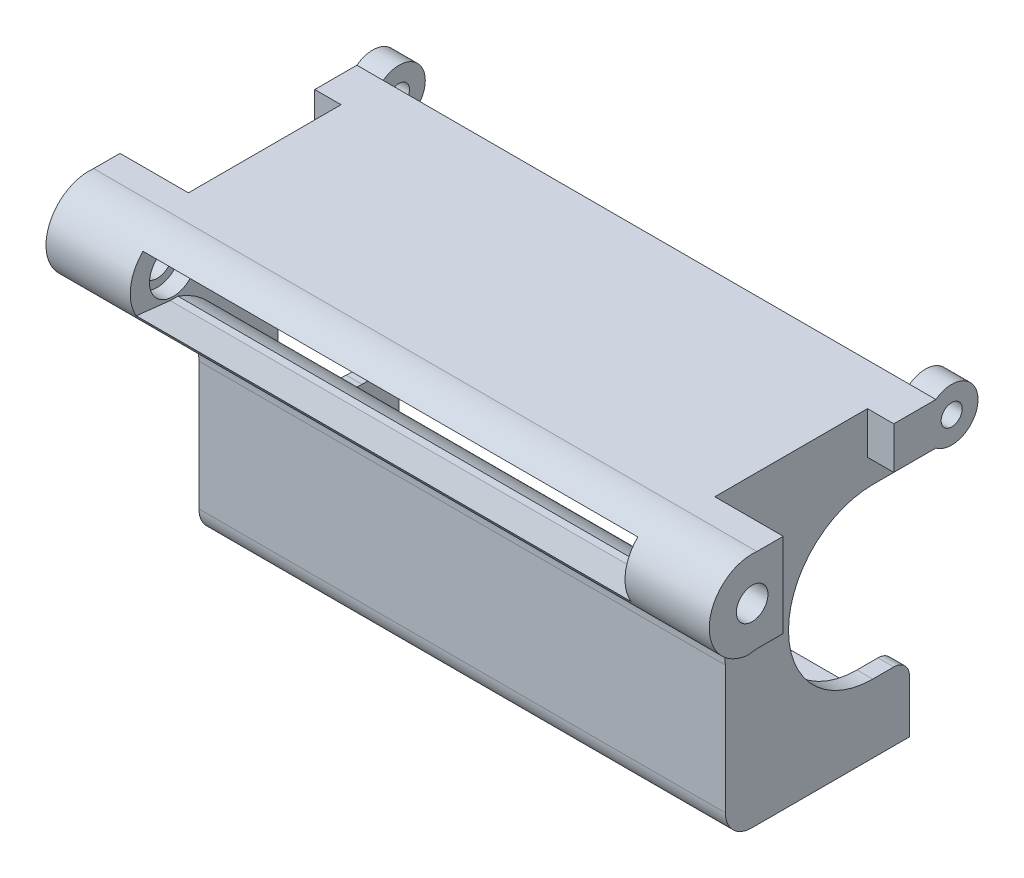
SolidWorks part; units mm, degrees
ref_plane "前视基准面" through (0, 0, 0) normal (0, 0, 1) x (1, 0, 0)
ref_plane "上视基准面" through (0, 0, 0) normal (0, 1, 0) x (1, 0, 0)
ref_plane "右视基准面" through (0, 0, 0) normal (1, 0, 0) x (0, 0, -1)
sketch "草图1" plane through (0, 0, 0) normal (0, 0, 1) x (1, 0, 0)
  line L1 (63, -8) -> (-63, -8)
  line L2 (63, -8) -> (63, 8)
  line L3 (63, 8) -> (-63, 8)
  line L4 (-63, -8) -> (-63, 8)
  line L5 (63, -8) -> (-63, 8) construction
  line L6 (63, 8) -> (-63, -8) construction
  line L7 (60, -5) -> (-60, -5)
  line L8 (60, -5) -> (60, 5)
  line L9 (60, 5) -> (-60, 5)
  line L10 (-60, -5) -> (-60, 5)
  line L11 (60, -5) -> (-60, 5) construction
  line L12 (60, 5) -> (-60, -5) construction
  point P0 (0, 0)
  point P6 (0, 0)
  dimension "D1" = 3
  dimension "D2" = 3
extrude "凸台-拉伸1" add sketch "草图1" along normal blind 70
sketch "草图2" plane through (0, 0, 70) normal (0, 0, 1) x (1, 0, 0)
  line L0 (0, 5) -> (0, -5) construction
  line L1 (60, 5) -> (-60, 5) construction
  line L2 (-60, -5) -> (60, -5) construction
  line L4 (2.7049, -5) -> (-2.7049, -5)
  line L5 (2.7049, -5) -> (2.7049, 5)
  line L6 (2.7049, 5) -> (-2.7049, 5)
  line L7 (-2.7049, -5) -> (-2.7049, 5)
  line L8 (2.7049, -5) -> (-2.7049, 5) construction
  line L9 (2.7049, 5) -> (-2.7049, -5) construction
  point P6 (0, 0)
extrude "凸台-拉伸2" add sketch "草图2" against normal blind 70
fillet "圆角4" radius 3 1 edges at (-2.7049, -5, 35)
fillet "圆角5" radius 3 1 edges at (-2.7049, 5, 35)
ref_plane "基准面1" through (0, 0, 2) normal (0, 0, -1) x (-1, 0, 0)
sketch "草图5" plane through (0, 0, 2) normal (0, 0, -1) x (-1, 0, 0)
  line L0 (-72, 0) -> (-69, 0) construction
  line L1 (-63, -8) -> (-63, 8) construction
  line L3 (-63, 3.5) -> (-63, -3.5)
  line L4 (-63, -3.5) -> (-72, -3.5)
  line L6 (-63, 3.5) -> (-72, 3.5)
  line L7 (-72, -3.5) -> (-72, 3.5)
  line L8 (-63, 0) -> (-72, 3.5) construction
  line L9 (-63, 0) -> (-72, -3.5) construction
  circle A1 centre (-69, 0) radius 1.6
  dimension "D1" = 9
extrude "凸台-拉伸3" add sketch "草图5" against normal blind 4
fillet "圆角7" radius 2 4 edges at (63, -3.5, 4) (72, -3.5, 4) (72, 3.5, 4) (63, 3.5, 4)
mirror "镜向8" about plane through (0, 0, 0) normal (1, 0, 0) of bodies 108
ref_plane "基准面3" through (0, 0, 35) normal (0, 0, -1) x (-1, 0, 0)
mirror "镜向11" about plane through (0, 0, 35) normal (0, 0, -1) of bodies 112
sketch "草图7" plane through (0, -8, 0) normal (0, -1, 0) x (1, 0, 0)
  line L0 (0, 0) -> (0, 70) construction
  line L1 (-63, 70) -> (63, 70) construction
  line L2 (-25, 0) -> (-25, 70) construction
  line L3 (-63, 0) -> (63, 0) construction
  line L4 (-42, 0) -> (-42, 70) construction
  line L5 (-63, 6) -> (63, 6) construction
  line L6 (-63, 9) -> (63, 9) construction
  line L7 (-63, 70) -> (-63, 0) construction
  line L8 (63, 70) -> (63, 0) construction
  line L9 (-43.6, 21) -> (-43.6, 9)
  line L10 (-40.4, 21) -> (-40.4, 9)
  line L11 (-42, 70) -> (-25, 70) construction
  line L12 (-33.5, 70) -> (-33.5, 0) construction
  line L13 (-26.6, 21) -> (-26.6, 9)
  line L14 (-23.4, 21) -> (-23.4, 9)
  line L15 (23.4, 21) -> (23.4, 9)
  line L16 (26.6, 21) -> (26.6, 9)
  line L17 (40.4, 21) -> (40.4, 9)
  line L18 (43.6, 21) -> (43.6, 9)
  arc A0 (-43.6, 9) -> (-40.4, 9) centre (-42, 9) ccw
  arc A1 (-40.4, 21) -> (-43.6, 21) centre (-42, 21) ccw
  arc A2 (-26.6, 21) -> (-23.4, 21) centre (-25, 21) cw
  arc A3 (-23.4, 9) -> (-26.6, 9) centre (-25, 9) cw
  arc A4 (23.4, 9) -> (26.6, 9) centre (25, 9) ccw
  arc A5 (26.6, 21) -> (23.4, 21) centre (25, 21) ccw
  arc A6 (40.4, 21) -> (43.6, 21) centre (42, 21) cw
  arc A7 (43.6, 9) -> (40.4, 9) centre (42, 9) cw
  dimension "D4" = 12
  dimension "D1" = 25
  dimension "D2" = 17
  dimension "D3" = 3
extrude "切除-拉伸2" cut sketch "草图7" against normal blind 4
fillet "圆角11" radius 2 12 edges at (-32.8524, 5, 0) (-3.5835, 4.1213, 0) (-32.8524, -5, 0) (-3.5835, -4.1213, 0) (32.8524, -5, 0) (3.5835, -4.1213, 0) (32.8524, 5, 0) (3.5835, 4.1213, 0) (60, 0, 0) (-60, 0, 0) (-2.7049, 0, 0) (2.7049, 0, 0)
fillet "圆角12" radius 2 12 edges at (-32.8524, 5, 70) (-3.5835, 4.1213, 70) (-2.7049, 0, 70) (-3.5835, -4.1213, 70) (32.8524, 5, 70) (3.5835, 4.1213, 70) (2.7049, 0, 70) (3.5835, -4.1213, 70) (-60, 0, 70) (-32.8524, -5, 70) (60, 0, 70) (32.8524, -5, 70)
ref_plane "基准面4" through (0, 0, -10) normal (0, 0, -1) x (-1, 0, 0)
sketch "草图9" plane through (0, 0, -10) normal (0, 0, -1) x (-1, 0, 0)
  line L1 (63, -8) -> (-63, -8)
  line L2 (63, -8) -> (63, 8)
  line L3 (63, 8) -> (-63, 8)
  line L4 (-63, -8) -> (-63, 8)
  line L5 (60, -5) -> (-60, -5)
  line L6 (60, -5) -> (60, 5)
  line L7 (60, 5) -> (-60, 5)
  line L8 (-60, -5) -> (-60, 5)
extrude "凸台-拉伸4" add sketch "草图9" along normal blind 5 separate body
sketch "草图10" plane through (0, 0, -10) normal (0, 0, -1) x (-1, 0, 0)
  line L0 (-63, -8) -> (63, -8) construction
  line L1 (-50, 8) -> (50, 8)
  line L2 (-50, 8) -> (-50, -8)
  line L3 (-50, -8) -> (50, -8)
  line L4 (50, 8) -> (50, -8)
  line L5 (-50, 8) -> (50, -8) construction
  line L6 (-50, -8) -> (50, 8) construction
  line L7 (-60, -5) -> (60, -5) construction
  line L8 (-47, 5) -> (47, 5)
  line L9 (-47, 5) -> (-47, -5)
  line L10 (-47, -5) -> (47, -5)
  line L11 (47, 5) -> (47, -5)
  line L12 (-47, 5) -> (47, -5) construction
  line L13 (-47, -5) -> (47, 5) construction
  point P0 (0, 0)
  point P8 (0, 0)
  dimension "D1" = 3
  dimension "D2" = 100
extrude "凸台-拉伸5" add sketch "草图10" along normal blind 7
sketch "草图11" plane through (0, 0, -15) normal (0, 0, -1) x (-1, 0, 0)
  line L0 (50, -8) -> (50, 8) construction
  line L1 (60, -5) -> (50, -5)
  line L2 (60, -5) -> (60, 5)
  line L3 (60, 5) -> (50, 5)
  line L4 (50, -5) -> (50, 5)
  line L5 (60, 5) -> (50, 5) construction
  line L7 (-60, -5) -> (-50, -5)
  line L8 (-60, -5) -> (-60, 5)
  line L9 (-60, 5) -> (-50, 5)
  line L10 (-50, -5) -> (-50, 5)
extrude "凸台-拉伸6" add sketch "草图11" against normal up to surface (5 mm away) up to face at (-55, 0, -10)
sketch "草图13" plane through (-50, 0, 0) normal (-1, 0, 0) x (0, 0, 1)
  line L1 (-17, 8) -> (-45, 8)
  line L2 (-17, 8) -> (-17, -50)
  line L3 (-17, -50) -> (-45, -50)
  line L4 (-45, 8) -> (-45, -50)
  dimension "D1" = 58
  dimension "D2" = 28
extrude "凸台-拉伸7" add sketch "草图13" against normal up to surface (100 mm away) up to face at (50, 0, -16)
sketch "草图14" plane through (0, 0, -45) normal (0, 0, -1) x (-1, 0, 0)
  line L1 (50, -50) -> (-50, -50)
  line L2 (50, -50) -> (50, 8)
  line L3 (50, 8) -> (-50, 8)
  line L4 (-50, -50) -> (-50, 8)
  line L5 (47, -47) -> (-47, -47)
  line L6 (47, -47) -> (47, 5)
  line L7 (47, 5) -> (-47, 5)
  line L8 (-47, -47) -> (-47, 5)
  dimension "D1" = 3
  dimension "D2" = 3
  dimension "D3" = 3
  dimension "D4" = 3
extrude "切除-拉伸3" cut sketch "草图14" against normal blind 25 contours L6 L5 L8 L7
sketch "草图15" plane through (0, 0, -17) normal (0, 0, 1) x (1, 0, 0)
  line L4 (47, 5) -> (-47, 5)
  line L5 (-47, 5) -> (-47, -5)
  line L6 (-47, -5) -> (47, -5)
  line L7 (47, -5) -> (47, 5)
  line L8 (47, 5) -> (-47, 5)
  line L9 (-47, 5) -> (-47, -5)
  line L10 (-47, -5) -> (47, -5)
  line L11 (47, -5) -> (47, 5)
  dimension "D1" = 0
extrude "切除-拉伸4" cut sketch "草图15" against normal blind 32
sketch "草图18" plane through (0, -50, 0) normal (0, -1, 0) x (1, 0, 0)
  line L0 (0, -17) -> (0, -45) construction
  line L2 (50, -17) -> (-50, -17) construction
  line L3 (50, -45) -> (-50, -45) construction
  line L4 (-20, -27) -> (20, -27)
  line L5 (20, -17) -> (-20, -17)
  line L6 (20, -17) -> (20, -45)
  line L7 (20, -45) -> (-20, -45)
  line L8 (-20, -17) -> (-20, -45)
  line L9 (20, -17) -> (-20, -45) construction
  line L10 (20, -45) -> (-20, -17) construction
  point P7 (0, -31)
  line M9 (-50, -45) -> (50, -45)
  dimension "D1" = 10
extrude "切除-拉伸6" cut sketch "草图18" against normal blind 12 contours L4 L8 L6 M9 region at (0, -50, -36)
sketch "草图20" plane through (50, 0, 0) normal (1, 0, 0) x (0, 0, -1)
  line L0 (45, -50) -> (45, 8) construction
  circle A0 centre (45, -21) radius 16
extrude "切除-拉伸8" cut sketch "草图20" against normal through all
fillet "圆角14" radius 3 4 edges at (20, -48.5, -45) (20, -48.5, -27) (-20, -48.5, -27) (-20, -48.5, -45)
fillet "圆角15" radius 15 1 edges at (0, -8, -17)
fillet "圆角16" radius 15 1 edges at (0, -5, -20)
sketch "草图22" plane through (0, 0, -10) normal (0, 0, -1) x (-1, 0, 0)
  line L0 (-50, -13.2053) -> (-50, -20.6886) construction
  line L1 (-63, 8) -> (-50, 8)
  line L2 (-63, 8) -> (-63, -2.2383)
  line L3 (-63, -2.2383) -> (-50, -2.2383)
  line L4 (-50, 8) -> (-50, -2.2383)
  line L5 (0, 0) -> (0, -50) construction
  line L6 (-50, -50) -> (50, -50) construction
  line L7 (50, 8) -> (50, -2.2383)
  line L8 (63, -2.2383) -> (50, -2.2383)
  line L9 (63, 8) -> (63, -2.2383)
  line L10 (63, 8) -> (50, 8)
  line L12 (-50, -2.2383) -> (-70.1223, -2.2383)
  line L13 (-50, -2.2383) -> (-50, -20.1302)
  line L14 (-50, -20.1302) -> (-70.1223, -20.1302)
  line L15 (-70.1223, -2.2383) -> (-70.1223, -20.1302)
  line L16 (50, -2.2383) -> (70.4029, -2.2383)
  line L17 (50, -2.2383) -> (50, -24.2485)
  line L18 (50, -24.2485) -> (70.4029, -24.2485)
  line L19 (70.4029, -2.2383) -> (70.4029, -24.2485)
  dimension "D1" = 0
extrude "切除-拉伸9" cut sketch "草图22" along normal blind 35 contours L12 L15 L14 L13 L3 | L19 L16 L8 L17 L18 region at (60.0611, -11.1843, -10) region at (-60.2015, -13.2434, -10)
sketch "草图23" plane through (0, -2.2383, 0) normal (0, -1, 0) x (1, 0, 0)
  line L0 (-50, -10) -> (-63, -10) construction
  line L1 (50, -15) -> (63, -15)
  line L2 (50, -15) -> (50, -10)
  line L3 (50, -10) -> (63, -10)
  line L4 (63, -15) -> (63, -10)
  line L5 (-63, -15) -> (-53, -15)
  line L6 (-63, -15) -> (-63, -10)
  line L7 (-63, -10) -> (-53, -10)
  line L8 (-53, -15) -> (-53, -10)
extrude "凸台-拉伸9" add sketch "草图23" along normal up to surface (5.7617 mm away) up to face at (-42, -8, 15)
sketch "草图26" plane through (-63, 0, 0) normal (-1, 0, 0) x (0, 0, 1)
  line L0 (-10, -8) -> (-10, 8)
  line L4 (-10, -8) -> (-8.195, -8.2063)
  line L5 (-10, 8) -> (-8.195, -8.2063)
extrude "凸台-拉伸10" add sketch "草图26" against normal up to surface (126 mm away) up to face at (63, 0, -12.5)
sketch "草图27" plane through (0, 0, -10) normal (0, 0, -1) x (-1, 0, 0)
  line L4 (-47, -5) -> (47, -5)
  line L5 (47, -5) -> (47, 5)
  line L6 (47, 5) -> (-47, 5)
  line L7 (-47, 5) -> (-47, -5)
  line L8 (-47, -5) -> (47, -5)
  line L9 (47, -5) -> (47, 5)
  line L10 (47, 5) -> (-47, 5)
  line L11 (-47, 5) -> (-47, -5)
  dimension "D1" = 0
extrude "切除-拉伸11" cut sketch "草图27" against normal blind 5
ref_plane "基准面5" through (0, -1.5556, -13.9667) normal (0, 0.1107, 0.9939) x (1, 0, 0)
sketch "草图29" plane through (0, -1.5556, -13.9667) normal (0, 0.1107, 0.9939) x (1, 0, 0)
  line L0 (63, 9.6112) -> (63, -6.2905)
  line L1 (63, 5.2448) -> (63, -1.8396)
  line L2 (63, -1.8396) -> (72, -1.8396)
  line L4 (63, 5.1604) -> (72, 5.1604)
  line L5 (72, -1.8396) -> (72, 5.1604)
  line L6 (63, 1.6604) -> (72, 5.1604) construction
  line L7 (63, 1.6604) -> (72, -1.8396) construction
  line L8 (72, 1.6604) -> (69, 1.6604) construction
  line L9 (0, 0) -> (0, 30.0975) construction
  line L10 (-72, 1.6604) -> (-69, 1.6604) construction
  line L11 (-63, 1.6604) -> (-72, -1.8396) construction
  line L12 (-63, 1.6604) -> (-72, 5.1604) construction
  line L13 (-72, -1.8396) -> (-72, 5.1604)
  line L14 (-63, 5.1604) -> (-72, 5.1604)
  line L15 (-63, -1.8396) -> (-72, -1.8396)
  line L16 (-63, 5.2448) -> (-63, -1.8396)
  circle A0 centre (69, 1.6604) radius 1.6
  circle A1 centre (-69, 1.6604) radius 1.6
  point P4 (63, 1.6604)
extrude "凸台-拉伸11" add sketch "草图29" along normal blind 4 contours L16 L14 L13 L15 A1 | L2 L5 L4 L1 A0 region at (67.2805, 0.0946, -14.1504) region at (-67.2805, 0.0946, -14.1504)
fillet "圆角19" radius 2 4 edges at (63, -3.1625, -11.7753) (72, -3.1625, -11.7753) (72, 3.7945, -12.5502) (63, 3.7945, -12.5502)
fillet "圆角20" radius 2 4 edges at (-63, -3.1625, -11.7753) (-72, -3.1625, -11.7753) (-72, 3.7945, -12.5502) (-63, 3.7945, -12.5502)
fillet "圆角21" radius 5 1 edges at (0, -50, -17)
fillet "圆角22" radius 5 1 edges at (0, -47, -20)
sketch "草图30" plane through (63, 0, 0) normal (1, 0, 0) x (0, 0, -1)
  line L1 (3.0672, -11.165) -> (-76.2951, -11.165)
  line L2 (3.0672, -11.165) -> (3.0672, 13.3763)
  line L3 (3.0672, 13.3763) -> (-76.2951, 13.3763)
  line L4 (-76.2951, -11.165) -> (-76.2951, 13.3763)
extrude "切除-拉伸12" cut sketch "草图30" against normal through all and the other way through all
sketch "草图31" plane through (0, 0, -45) normal (0, 0, -1) x (-1, 0, 0)
  line L0 (47, -5) -> (50, -5) construction
  line L1 (50, -5) -> (50, 8) construction
  line L2 (50, 8) -> (-50, 8) construction
  line L3 (-50, 8) -> (-50, -5) construction
  line L4 (-50, -5) -> (-47, -5) construction
  line L5 (-47, -5) -> (-47, 5) construction
  line L6 (-47, 5) -> (47, 5) construction
  line L7 (47, 5) -> (47, -5) construction
  line L8 (-50, -50) -> (-23, -50) construction
  line L9 (-23, -50) -> (-23, -47) construction
  line L10 (-23, -47) -> (-47, -47) construction
  line L11 (-47, -47) -> (-47, -37) construction
  line L12 (-47, -37) -> (-50, -37) construction
  line L13 (-50, -37) -> (-50, -50) construction
  line L14 (47, -47) -> (23, -47) construction
  line L15 (23, -47) -> (23, -50) construction
  line L16 (23, -50) -> (50, -50) construction
  line L17 (50, -50) -> (50, -37) construction
  line L18 (50, -37) -> (47, -37) construction
  line L19 (47, -37) -> (47, -47) construction
  line L20 (47, -5) -> (50, -5)
  line L21 (50, -5) -> (50, 8)
  line L22 (50, 8) -> (-50, 8)
  line L23 (-50, 8) -> (-50, -5)
  line L24 (-50, -5) -> (-47, -5)
  line L25 (-47, -5) -> (-47, 5)
  line L26 (-47, 5) -> (47, 5)
  line L27 (47, 5) -> (47, -5)
  line L28 (-50, -50) -> (-23, -50)
  line L29 (-23, -50) -> (-23, -47)
  line L30 (-23, -47) -> (-47, -47)
  line L31 (-47, -47) -> (-47, -37)
  line L32 (-47, -37) -> (-50, -37)
  line L33 (-50, -37) -> (-50, -50)
  line L34 (47, -47) -> (23, -47)
  line L35 (23, -47) -> (23, -50)
  line L36 (23, -50) -> (50, -50)
  line L37 (50, -50) -> (50, -37)
  line L38 (50, -37) -> (47, -37)
  line L39 (47, -37) -> (47, -47)
extrude "凸台-拉伸12" add sketch "草图31" along normal blind 7
sketch "草图32" plane through (0, 0, -20) normal (0, 0, -1) x (-1, 0, 0)
  line L0 (47, -42) -> (47, -19.1421) construction
  line L1 (47, -41) -> (-47, -41)
  line L2 (47, -41) -> (47, -37)
  line L3 (47, -37) -> (-47, -37)
  line L4 (-47, -41) -> (-47, -37)
  line L5 (0, -41) -> (0, -37)
  line L6 (-17.0982, -41) -> (-17.0982, -37)
  line L7 (43.5466, -41) -> (34.684, -41)
  line L8 (43.5466, -41) -> (43.5466, -37)
  line L9 (43.5466, -37) -> (34.684, -37)
  line L10 (34.684, -41) -> (34.684, -37)
  line L11 (25.4026, -41) -> (17.0982, -41)
  line L12 (25.4026, -41) -> (25.4026, -37)
  line L13 (25.4026, -37) -> (17.0982, -37)
  line L14 (17.0982, -41) -> (17.0982, -37)
  line L15 (-4.8858, -37) -> (4.8858, -37)
  line L16 (-4.8858, -37) -> (-4.8858, -41)
  line L17 (-4.8858, -41) -> (4.8858, -41)
  line L18 (4.8858, -37) -> (4.8858, -41)
  line L19 (-4.8858, -37) -> (4.8858, -41) construction
  line L20 (-4.8858, -41) -> (4.8858, -37) construction
  line L21 (-25.4026, -37) -> (-17.0982, -37)
  line L22 (-25.4026, -41) -> (-25.4026, -37)
  line L23 (-25.4026, -41) -> (-17.0982, -41)
  line L24 (-34.684, -41) -> (-34.684, -37)
  line L25 (-43.5466, -37) -> (-34.684, -37)
  line L26 (-43.5466, -41) -> (-43.5466, -37)
  line L27 (-43.5466, -41) -> (-34.684, -41)
  point P17 (0, -39)
extrude "凸台-拉伸13" add sketch "草图32" along normal blind 7 contours L10 L1 L8 L3 | L14 L1 L12 L3 | L18 L3 L5 L1 | L3 L16 L1 L5 | L22 L1 L6 L3 | L26 L1 L24 L3 region at (-39.1153, -39, -20) region at (-21.2504, -39, -20) region at (-2.4429, -39, -20) region at (2.4429, -39, -20) region at (21.2504, -39, -20) region at (39.1153, -39, -20)
fillet "圆角23" radius 2 10 edges at (43.5466, -39, -20) (34.684, -39, -20) (25.4026, -39, -20) (17.0982, -39, -20) (4.8858, -39, -20) (-4.8858, -39, -20) (-17.0982, -39, -20) (-25.4026, -39, -20) (-34.684, -39, -20) (-43.5466, -39, -20)
fillet "圆角24" radius 2 10 edges at (43.5466, -39, -27) (34.684, -39, -27) (25.4026, -39, -27) (17.0982, -39, -27) (4.8858, -39, -27) (-4.8858, -39, -27) (-17.0982, -39, -27) (-25.4026, -39, -27) (-34.684, -39, -27) (-43.5466, -39, -27)
sketch "草图33" plane through (0, -50, 0) normal (0, -1, 0) x (1, 0, 0)
  line L1 (-20, -42) -> (-23, -42)
  line L2 (-20, -42) -> (-20, -52)
  line L3 (-20, -52) -> (-23, -52)
  line L4 (-23, -42) -> (-23, -52)
  line L5 (20, -42) -> (23, -42)
  line L6 (20, -42) -> (20, -52)
  line L7 (20, -52) -> (23, -52)
  line L8 (23, -42) -> (23, -52)
extrude "凸台-拉伸14" add sketch "草图33" against normal up to surface (3 mm away) up to face at (0, -47, -39)
fillet "圆角25" radius 3 2 edges at (20, -48.5, -52) (-20, -48.5, -52)
fillet "圆角26" radius 3 4 edges at (48.5, -37, -52) (48.5, -5, -52) (-48.5, -5, -52) (-48.5, -37, -52)
sketch "草图34" plane through (-47, 0, 0) normal (1, 0, 0) x (0, 0, -1)
  line L0 (52, 7.6) -> (36.7891, 5)
  line L1 (52, 8) -> (52, -2) construction
  line L2 (52, 5) -> (9.6659, 5) construction
  line L7 (36.7891, 5) -> (52, 5)
  line L8 (52, 5) -> (52, 7.6)
extrude "切除-拉伸13" cut sketch "草图34" along normal up to surface (94 mm away) up to face at (47, -20.042, -33.9766)
fillet "圆角27" radius 30 1 edges at (0, 5, -36.7891)
sketch "草图35" plane through (0, 0, -15) normal (0, 0, -1) x (-1, 0, 0)
  line L1 (53, -8) -> (50, -8)
  line L2 (53, -8) -> (53, -2.2383)
  line L3 (53, -2.2383) -> (50, -2.2383)
  line L4 (50, -8) -> (50, -2.2383)
extrude "凸台-拉伸15" add sketch "草图35" against normal up to surface (5 mm away) up to face at (-51.5, -5.1192, -10)
sketch "草图36" plane through (0, -1.0021, -8.9974) normal (0, 0.1107, 0.9939) x (1, 0, 0)
  line L1 (-63, -7.2487) -> (-82.4037, -7.2487)
  line L2 (-63, -7.2487) -> (-63, 11.3943)
  line L3 (-63, 11.3943) -> (-82.4037, 11.3943)
  line L4 (-82.4037, -7.2487) -> (-82.4037, 11.3943)
  line L5 (-63, -7.2487) -> (-82.4037, 11.3943) construction
  line L6 (-63, 11.3943) -> (-82.4037, -7.2487) construction
  line L7 (63, -7.2487) -> (83.9123, -7.2487)
  line L8 (63, -7.2487) -> (63, 17.533)
  line L9 (63, 17.533) -> (83.9123, 17.533)
  line L10 (83.9123, -7.2487) -> (83.9123, 17.533)
  line L11 (63, -7.2487) -> (83.9123, 17.533) construction
  line L12 (63, 17.533) -> (83.9123, -7.2487) construction
  point P4 (-72.7019, 2.0728)
  point P10 (73.4562, 5.1421)
extrude "切除-拉伸14" cut sketch "草图36" against normal blind 10
sketch "草图37" plane through (63, 0, 0) normal (1, 0, 0) x (0, 0, -1)
  line L0 (8.195, -8.2063) -> (10, 8)
  line L1 (10, 8) -> (8.195, -8.2063) construction
  arc A0 (10, 8) -> (8.195, -8.2063) centre (9.0975, -0.1031) ccw
  point P2 (10, 8.0501)
extrude "凸台-拉伸16" add sketch "草图37" against normal up to surface (126 mm away) up to face at (-63, -1.6413, -11.639)
sketch "草图38" plane through (0, -1.0021, -8.9974) normal (0, -0.1107, -0.9939) x (-1, 0, 0)
  line L4 (47, -4.0226) -> (47, 6.0392)
  line L5 (47, 6.0392) -> (-47, 6.0392)
  line L6 (-47, 6.0392) -> (-47, -4.0226)
  line L7 (-47, -4.0226) -> (47, -4.0226)
  line L8 (47, -4.0226) -> (47, 6.0392)
  line L9 (47, 6.0392) -> (-47, 6.0392)
  line L10 (-47, 6.0392) -> (-47, -4.0226)
  line L11 (-47, -4.0226) -> (47, -4.0226)
  dimension "D1" = 0
extrude "切除-拉伸15" cut sketch "草图38" against normal blind 10
sketch "草图39" plane through (0, 0, 0) normal (1, 0, 0) x (0, 0, -1)
  circle A0 centre (9.0975, -0.1031) radius 4.5
  dimension "D1" = 9
extrude "切除-拉伸16" cut sketch "草图39" against normal mid plane 100
sketch "草图40" plane through (-63, 0, 0) normal (-1, 0, 0) x (0, 0, 1)
  circle A0 centre (-9.0975, -0.1031) radius 3
  dimension "D1" = 6
extrude "切除-拉伸17" cut sketch "草图40" against normal through all and the other way through all
sketch "草图41" plane through (50, 0, 0) normal (1, 0, 0) x (0, 0, -1)
  line L0 (52, 8) -> (15, 8) construction
  line L1 (44, 8) -> (55, 8)
  line L2 (44, 8) -> (44, 0)
  line L3 (44, 0) -> (55, 0)
  line L4 (55, 8) -> (55, 0)
  line L5 (44, 8) -> (55, 0) construction
  line L6 (44, 0) -> (55, 8) construction
  line L7 (52, 8) -> (52, -2) construction
  circle A0 centre (55, 4) radius 5
  point P4 (49.5, 4)
  point P11 (68.3894, 4)
  line M9 (52, -2) -> (52, 8)
  line M10 (52, 8) -> (15, 8)
  dimension "D3" = 10
  dimension "D1" = 8
  dimension "D2" = 8
  dimension "D4" = 3
extrude "凸台-拉伸17" add sketch "草图41" along normal blind 5 contours A0 L2 L3 M10 | L3 A0 L1 L4 | L4 L1 L3 M9 | A0 M9 region at (50, 4, -47.3258) region at (50, 4, -56.8144) region at (50, 4, -51.1845) region at (50, 4, -53.5)
mirror "镜向12" about plane through (0, 0, 0) normal (1, 0, 0) of "凸台-拉伸17"
sketch "草图42" plane through (-50, 0, 0) normal (1, 0, 0) x (0, 0, -1)
  circle A0 centre (55, 4) radius 2
  dimension "D1" = 4
extrude "切除-拉伸18" cut sketch "草图42" against normal through all both and the other way through all
